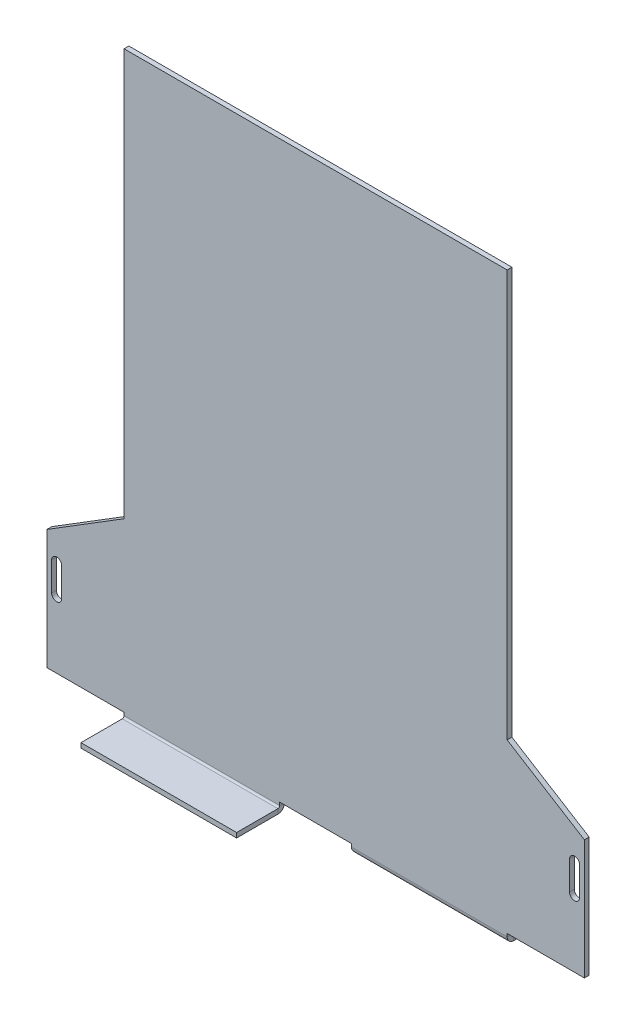
SolidWorks part; units mm, degrees
note: The reader was unsure of these and kept them because the rebuilt part matched: flange length of "Edge-Flange1", "Edge-Flange2".
ref_plane "Front Plane" through (0, 0, 0) normal (0, 0, 1) x (1, 0, 0)
ref_plane "Top Plane" through (0, 0, 0) normal (0, 1, 0) x (1, 0, 0)
ref_plane "Right Plane" through (0, 0, 0) normal (1, 0, 0) x (0, 0, -1)
sketch "Sketch1" plane through (0, 0, 0) normal (0, 0, 1) x (1, 0, 0)
  line L0 (-108.16, -6) -> (-108.16, 6) construction
  line L1 (-110.26, -6) -> (-110.26, 6)
  line L2 (-106.06, -6) -> (-106.06, 6)
  line L3 (-80, 206) -> (-80, 36)
  line L6 (-80, 206) -> (80, 206)
  line L9 (108.16, -6) -> (108.16, 6) construction
  line L10 (106.06, -6) -> (106.06, 6)
  line L11 (110.26, -6) -> (110.26, 6)
  line L12 (-108.16, 0) -> (108.16, 0) construction
  line L14 (-112.26, -34) -> (-80, -34)
  line L16 (-80, 36) -> (-112.26, 16)
  line L17 (80, 206) -> (80, 36)
  line L18 (80, 36) -> (112.26, 16)
  line L19 (-80, 36) -> (80, 36) construction
  line L20 (0, 0) -> (0, 36) construction
  line L21 (-112.26, 16) -> (-112.26, -34)
  line L22 (112.26, 16) -> (112.26, -34)
  line L23 (-80, -34) -> (-80, -38)
  line L24 (-80, -38) -> (-15, -38)
  line L25 (-15, -38) -> (-15, -34)
  line L26 (80, -34) -> (80, -38)
  line L27 (80, -38) -> (15, -38)
  line L28 (15, -38) -> (15, -34)
  line L29 (-15, -36) -> (15, -36) construction
  line L30 (-15, -34) -> (15, -34)
  line L31 (0, -36) -> (0, 0) construction
  line L32 (80, -34) -> (112.26, -34)
  arc A0 (-110.26, -6) -> (-106.06, -6) centre (-108.16, -6) ccw
  arc A1 (-106.06, 6) -> (-110.26, 6) centre (-108.16, 6) ccw
  arc A6 (106.06, -6) -> (110.26, -6) centre (108.16, -6) ccw
  arc A7 (110.26, 6) -> (106.06, 6) centre (108.16, 6) ccw
  point P2 (-108.16, 0)
  point P21 (108.16, 0)
  dimension "D2" = 12
  dimension "D1" = 2.1
  dimension "D6" = 28
  dimension "D11" = 4
  dimension "D3" = 216.32
  dimension "D4" = 2
  dimension "D5" = 2
  dimension "D7" = 240
  dimension "D8" = 160
  dimension "D9" = 50
  dimension "D10" = 70
  dimension "D12" = 30
base flange "Base-Flange1" sketch "Sketch1" thickness 2 reverse thickness direction no parameters "D1"=0.7366
edge flange "Edge-Flange1" sketch "Sketch8" flange angle 90 flange length 20 flange position material inside bend radius 0.7366 thickness 2 relief rectangular parameters "D6"=10
sketch "Sketch8" plane through (0, -38, 0) normal (0, -1, 0) x (1, 0, 0)
  line L2 (-80, 0) -> (-80, 18)
  line L3 (-80, 18) -> (-15, 18)
  line L4 (-15, 18) -> (-15, 0)
  line L7 (-80, 0) -> (-15, 0) construction
  line L8 (-80, 0) -> (-15, 0)
bend "EdgeBend1" bend radius 0.7366 bend angle 90 parameters "D5"=1
edge flange "Edge-Flange2" sketch "Sketch11" flange angle 90 flange length 20 flange position material inside bend radius 0.7366 thickness 2 relief rectangular parameters "D6"=10
sketch "Sketch11" plane through (0, -38, -2) normal (0, -1, 0) x (-1, 0, 0)
  line L2 (-80, 0) -> (-80, 18)
  line L3 (-80, 18) -> (-15, 18)
  line L4 (-15, 18) -> (-15, 0)
  line L7 (-15, 0) -> (-80, 0) construction
  line L8 (-15, 0) -> (-80, 0)
bend "EdgeBend2" bend radius 0.7366 bend angle 90 parameters "D5"=2
sketch "Bend-Lines1" [suppressed] plane through (0, 0, 0) normal (0, 1, 0) x (1, 0, 0)
sketch "Bounding-Box1" [suppressed] plane through (0, 0, 0) normal (0, 1, 0) x (1, 0, 0)
sheet metal parameters "Sheet-Metal2" thickness 2 parameters "D1"=0.7366
flat pattern "Flat-Pattern2" [suppressed]
sketch "Bend-Lines2" plane through (0, 0, 0) normal (0, 1, 0) x (1, 0, 0)
sketch3d "Bounding-Box2" [suppressed]
  line L0 (114.36, 204, 0) -> (114.36, -38, 0) construction
  line L1 (-114.36, 204, 0) -> (-114.36, -38, 0) construction
  line L2 (114.36, 204, 0) -> (-114.36, 204, 0) construction
  line L3 (114.36, -38, 0) -> (-114.36, -38, 0) construction
sheet metal parameters "Sheet-Metal3" thickness 2 parameters "D1"=0.7366
flat pattern "Flat-Pattern2"
sketch "Bend-Lines2" plane through (0, 0, 0) normal (0, 0, 1) x (1, 0, 0)
  line L0 (-80, -38.6273) -> (-15, -38.6273) construction
  line L1 (-80, -38.6273) -> (-15, -38.6273) construction
sketch3d "Bounding-Box2" [suppressed]
  line L0 (114.36, 204, 0) -> (114.36, -47.2546, 0) construction
  line L1 (-114.36, 204, 0) -> (-114.36, -47.2546, 0) construction
  line L2 (114.36, 204, 0) -> (-114.36, 204, 0) construction
  line L3 (114.36, -47.2546, 0) -> (-114.36, -47.2546, 0) construction
bend of the flat pattern "Flatten-<EdgeBend1>1"
sheet metal parameters "Sheet-Metal4" thickness 2 parameters "D1"=0.7366
flat pattern "Flat-Pattern2"
sketch "Bend-Lines2" plane through (0, 0, 0) normal (0, 0, 1) x (1, 0, 0)
  line L0 (-80, -36.6273) -> (-15, -36.6273) construction
  line L1 (-80, -36.6273) -> (-15, -36.6273) construction
  line L2 (15, -36.6273) -> (80, -36.6273) construction
  line L3 (15, -36.6273) -> (80, -36.6273) construction
sketch3d "Bounding-Box2" [suppressed]
  line L0 (112.26, 206, 0) -> (112.26, -55.2546, 0) construction
  line L1 (-112.26, 206, 0) -> (-112.26, -55.2546, 0) construction
  line L2 (112.26, 206, 0) -> (-112.26, 206, 0) construction
  line L3 (112.26, -55.2546, 0) -> (-112.26, -55.2546, 0) construction
bend of the flat pattern "Flatten-<EdgeBend1>1"
bend of the flat pattern "Flatten-<EdgeBend2>1"
equation "\"acTubeOD\"= 300mm"
equation "\"acTubeThickness\"= 3mm"
equation "\"acTubeLength\"= 300mm"
equation "\"threadedRodDiam\"= 8mm"
equation "\"flange width\"= 24mm"
equation "\"elecPlateThick\"= 2mm"
